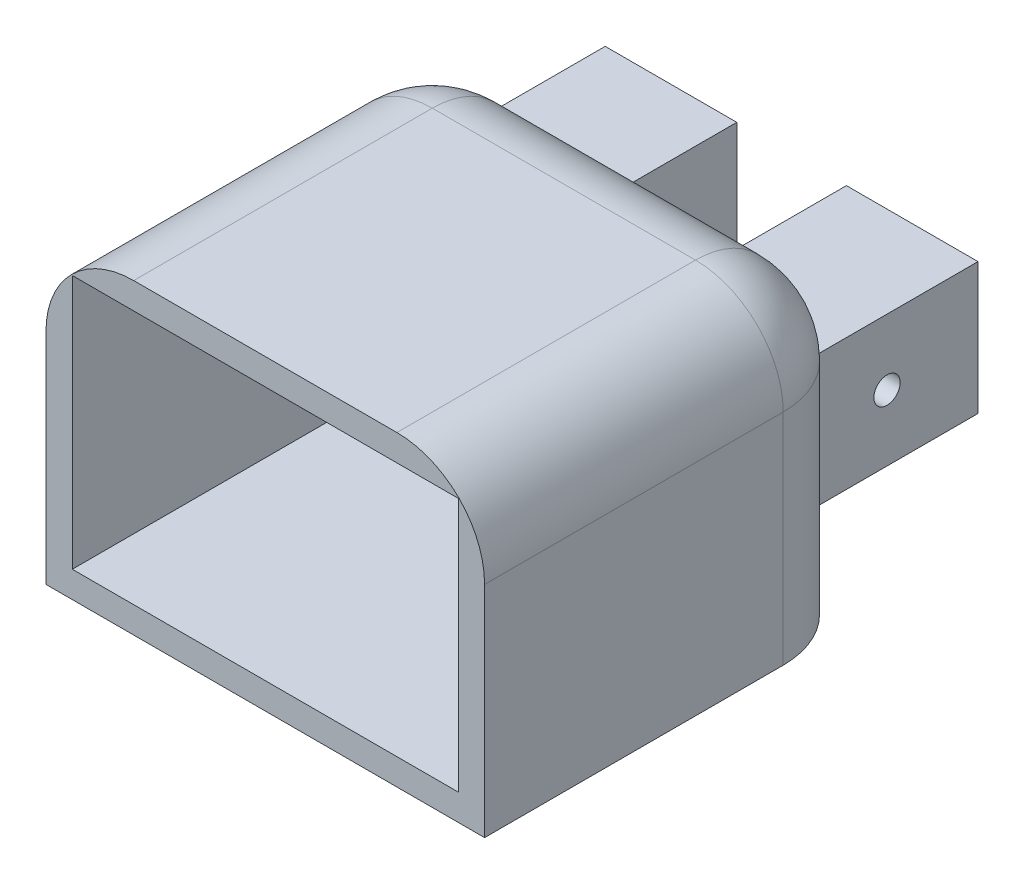
SolidWorks part; units mm, degrees
ref_plane "Front Plane" through (0, 0, 0) normal (0, 0, 1) x (1, 0, 0)
ref_plane "Top Plane" through (0, 0, 0) normal (0, 1, 0) x (1, 0, 0)
ref_plane "Right Plane" through (0, 0, 0) normal (1, 0, 0) x (0, 0, -1)
sketch "Sketch1" plane through (0, 0, 0) normal (0, 1, 0) x (1, 0, 0)
  line L6 (25, 0.2309) -> (25, -19.7691) construction
  line L7 (-25, 40.2309) -> (-25, -12.2693) construction
  line L8 (0, -19.7691) -> (25, -19.7691) construction
  line L9 (-25, 40.2309) -> (25, 40.2309) construction
  line L11 (-25, 40.2309) -> (25, 40.2309)
  line L12 (-25, 40.2309) -> (-25, -19.7691)
  line L13 (-25, -19.7691) -> (25, -19.7691)
  line L14 (25, 40.2309) -> (25, -19.7691)
  dimension "D1" = 60
extrude "Boss-Extrude1" add sketch "Sketch1" along normal blind 35
ref_plane "Plane1" through (0, 0, 19.7691) normal (0, 0, 1) x (1, 0, 0)
sketch "Sketch2" plane through (0, 0, 19.7691) normal (0, 0, 1) x (1, 0, 0)
  line L0 (0, 35) -> (0, 0) construction
  line L9 (-25, 35) -> (25, 35) construction
  line L10 (-25, 17.5) -> (25, 17.5) construction
  line L18 (-25, 35) -> (-25, 0) construction
  line L19 (25, 35) -> (25, 0) construction
  line L20 (22, 41.4768) -> (22, -7.1193) construction
  line L21 (-22, 40.336) -> (-22, -4.0773) construction
  line L22 (-26.0324, 3) -> (36.7091, 3) construction
  line L23 (-29.8349, 32) -> (46.0632, 32) construction
  line L24 (-25, 0) -> (25, 0) construction
  line L26 (-22, 32) -> (22, 32)
  line L27 (-22, 32) -> (-22, 3)
  line L28 (-22, 3) -> (22, 3)
  line L29 (22, 32) -> (22, 3)
  dimension "D1" = 3
  dimension "D2" = 3
  dimension "D3" = 3
  dimension "D4" = 3
extrude "Cut-Extrude1" cut sketch "Sketch2" against normal blind 30
ref_plane "Plane2" through (0, 0, -40.2309) normal (0, 0, -1) x (-1, 0, 0)
ref_plane "Plane3" through (0, 0, 0) normal (0, -1, 0) x (-1, 0, 0)
sketch "Sketch4" plane through (0, 0, 0) normal (0, -1, 0) x (-1, 0, 0)
  line L0 (-19.25, -19.7691) -> (19.25, -19.7691) construction
  line L1 (21.25, 40.2309) -> (21.25, -19.0959) construction
  line L2 (0, 15.2309) -> (21.25, 15.2309) construction
  line L3 (25, 21.2309) -> (-25, 21.2309) construction
  line L4 (25, 40.2309) -> (25, -19.7691) construction
  line L5 (-25, -19.7691) -> (-25, 40.2309) construction
  line L6 (25, 24.2749) -> (-25, 24.2749) construction
  line L7 (0, -18.8377) -> (0, 40.2309) construction
  line L8 (19.25, 40.2309) -> (-19.25, 40.2309) construction
  line L9 (2.5, 40.2309) -> (2.5, -19.7691) construction
  line L10 (-2.5, 40.2309) -> (-2.5, -19.7691) construction
  line L11 (6.25, -19.7691) -> (6.25, 40.2309) construction
  line L12 (-13.75, 40.2309) -> (-13.75, -21.1622) construction
  line L13 (13.75, -19.7691) -> (13.75, 40.2309) construction
  line L14 (-6.25, -19.7691) -> (-6.25, 40.2309) construction
  line L15 (-21.25, 40.2309) -> (-21.25, -19.7691) construction
  line L16 (-25, 24.2749) -> (-21.25, 24.2749)
  line L17 (-21.25, 24.2749) -> (-21.25, 40.2309)
  line L18 (-21.25, 40.2309) -> (-6.25, 40.2309)
  line L19 (-6.25, 40.2309) -> (-6.25, 24.2749)
  line L20 (-6.25, 24.2749) -> (6.25, 24.2749)
  line L21 (6.25, 24.2749) -> (6.25, 40.2309)
  line L22 (6.25, 40.2309) -> (21.25, 40.2309)
  line L23 (21.25, 40.2309) -> (21.25, 24.2749)
  line L24 (21.25, 24.2749) -> (25, 24.2749)
  line L25 (25, 24.2749) -> (38.2286, 24.2749)
  line L26 (38.2286, 24.2749) -> (38.2286, 61.6957)
  line L27 (38.2286, 61.6957) -> (-27.3618, 61.6957)
  line L28 (-27.3618, 61.6957) -> (-27.3618, 24.2749)
  line L29 (-27.3618, 24.2749) -> (-25, 24.2749)
  dimension "D1" = 35
  dimension "D2" = 6
  dimension "D3" = 2.5
  dimension "D4" = 2.5
  dimension "D5" = 11.25
  dimension "D6" = 11.25
  dimension "D7" = 7.5
  dimension "D8" = 7.5
  dimension "D9" = 7.5
  dimension "D10" = 7.5
extrude "Cut-Extrude2" cut sketch "Sketch4" against normal blind 36
ref_plane "Plane4" through (21.25, 0, 0) normal (1, 0, 0) x (0, 0, -1)
sketch "Sketch5" plane through (21.25, 0, 0) normal (1, 0, 0) x (0, 0, -1)
  line L0 (27.4652, 0) -> (32.2529, 35) construction
  line L1 (-27.5, 0) -> (27.5, 0) construction
  line L2 (24.2749, 35) -> (40.2309, 35) construction
  line L3 (40.2309, 17.3921) -> (-19.7691, 17.3921) construction
  line L4 (40.2309, -19.25) -> (40.2309, 19.25) construction
  line L5 (-19.7691, 19.25) -> (-19.7691, -19.25) construction
  circle A0 centre (29.859, 17.5) radius 1.5
  dimension "D1" = 3
extrude "Cut-Extrude3" cut sketch "Sketch5" against normal blind 48
ref_plane "Plane5" through (6.25, 0, 0) normal (-1, 0, 0) x (0, 0, 1)
sketch "Sketch6" plane through (6.25, 0, 0) normal (-1, 0, 0) x (0, 0, 1)
  circle A0 centre (-29.859, 17.5) radius 2.65
  dimension "D1" = 5.3
ref_plane "Plane7" through (-21.25, 0, 0) normal (-1, 0, 0) x (0, 0, 1)
sketch "Sketch12" plane through (-21.25, 0, 0) normal (-1, 0, 0) x (0, 0, 1)
  line L0 (-40.2309, 25) -> (-24.2749, 25) construction
  line L1 (-40.2309, 19.25) -> (-40.2309, -19.25) construction
  line L2 (-24.2749, 35) -> (-24.2749, 0) construction
  line L3 (-40.2309, 10) -> (-24.2749, 10) construction
  line L4 (-40.2309, 35) -> (-24.2749, 35) construction
  line L5 (-27.5, 0) -> (27.5, 0) construction
  line L6 (-40.2309, 10) -> (-24.2749, 10)
  line L7 (-24.2749, 10) -> (-24.2749, -4.8725)
  line L8 (-24.2749, -4.8725) -> (-41.9058, -4.8725)
  line L9 (-41.9058, -4.8725) -> (-41.9058, 36.9183)
  line L10 (-41.9058, 36.9183) -> (-24.2749, 36.9183)
  line L11 (-24.2749, 36.9183) -> (-24.2749, 25)
  line L12 (-24.2749, 25) -> (-40.2309, 25)
  line L13 (-40.2309, 25) -> (-40.2309, 10)
  dimension "D1" = 10
  dimension "D2" = 10
extrude "Cut-Extrude5" cut sketch "Sketch12" against normal blind 50.17
fillet "Fillet1" radius 10 1 edges at (0, 35, -24.2749)
fillet "Fillet2" radius 10 6 edges at (25, 12.5, -24.2749) (25, 32.0711, -21.346) (-25, 12.5, -24.2749) (-25, 32.0711, -21.346) (25, 35, 2.7471) (-25, 35, 2.7471)
